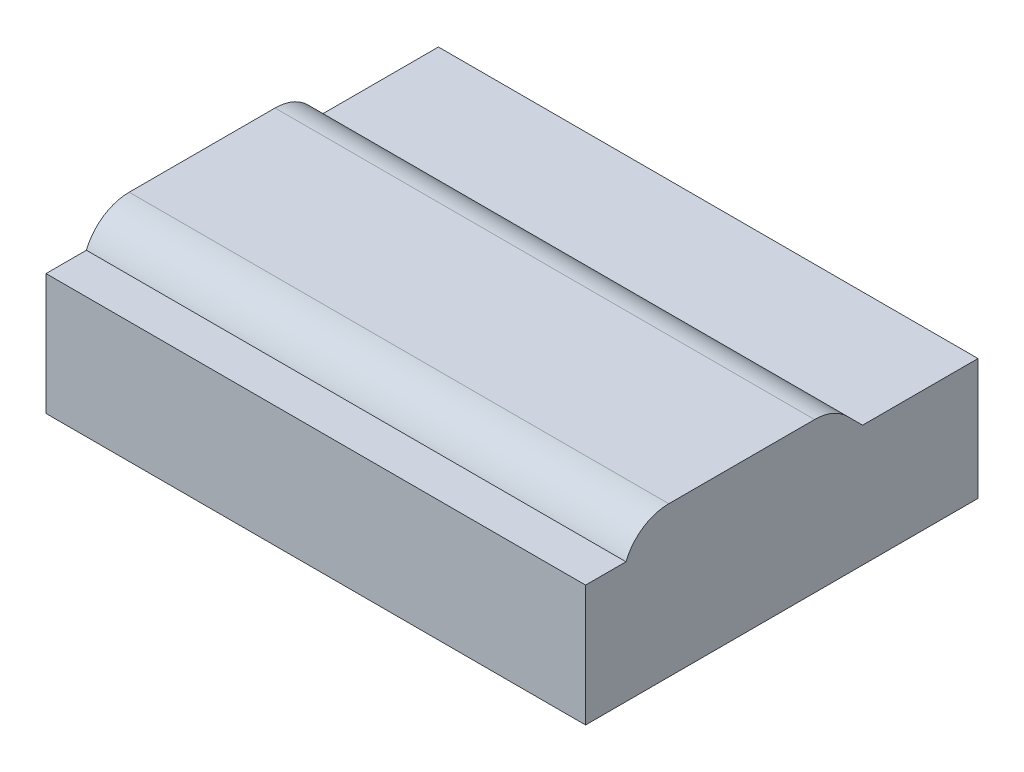
SolidWorks part; units mm, degrees
ref_plane "Front Plane" through (0, 0, 0) normal (0, 0, 1) x (1, 0, 0)
ref_plane "Top Plane" through (0, 0, 0) normal (0, 1, 0) x (1, 0, 0)
ref_plane "Right Plane" through (0, 0, 0) normal (1, 0, 0) x (0, 0, -1)
sketch "Sketch1" plane through (0, 0, 0) normal (0, 1, 0) x (1, 0, 0)
  line L1 (-467.5, 680) -> (467.5, 680)
  line L2 (-467.5, 680) -> (-467.5, 0)
  line L3 (-467.5, 0) -> (467.5, 0)
  line L4 (467.5, 680) -> (467.5, 0)
  point P4 (0, 680)
  dimension "D1" = 680
  dimension "D2" = 935
extrude "Boss-Extrude1" add sketch "Sketch1" against normal blind 210
sketch "Sketch3" plane through (-467.5, 0, 0) normal (-1, 0, 0) x (0, 0, 1)
  line L1 (-680, 0) -> (0, 0) construction
  line L2 (-70, 0) -> (-430, 0)
  line L3 (-70, 0) -> (-70, 50)
  line L4 (-70, 50) -> (-430, 50)
  line L5 (-430, 0) -> (-430, 50)
  line L6 (0, -210) -> (0, 0) construction
  line L7 (-430, 50) -> (-480, 0)
  line M1 (0, 0) -> (-680, 0)
  dimension "D2" = 70
  dimension "D1" = 50
  dimension "D3" = 360
  dimension "D4" = 50
extrude "Boss-Extrude2" add sketch "Sketch3" against normal up to surface (935 mm away) contours L5 L3 L4 M1 | L5 L7 M1 up to face at (467.5, -105, -340)
fillet "Fillet1" radius 80 2 edges at (0, 50, -70) (0, 50, -430)
sketch "Sketch4" plane through (0, 50, 0) normal (0, 1, 0) x (1, 0, 0)
  line L0 (-467.5, 270.5124) -> (467.5, 270.5124)
  line L1 (-467.5, 144.162) -> (-467.5, 396.8629) construction
  line L2 (467.5, 144.162) -> (467.5, 396.8629) construction
sketch3d "3DSketch1"
  line L0 (0, 50, -270.5124) -> (0, -210, -270.5124)
  line L1 (-467.5, 50, -270.5124) -> (467.5, 50, -270.5124) construction
  line L2 (467.5, 50, -270.5124) -> (-467.5, 50, -270.5124)
  line L3 (467.5, 50, -144.162) -> (467.5, 50, -396.8629) construction
  line L4 (-467.5, 50, -144.162) -> (-467.5, 50, -396.8629) construction
  line L5 (0, 50, -144.162) -> (0, 50, -396.8629)
  line L6 (-467.5, 50, -144.162) -> (467.5, 50, -144.162) construction
  line L7 (467.5, 50, -396.8629) -> (-467.5, 50, -396.8629) construction
